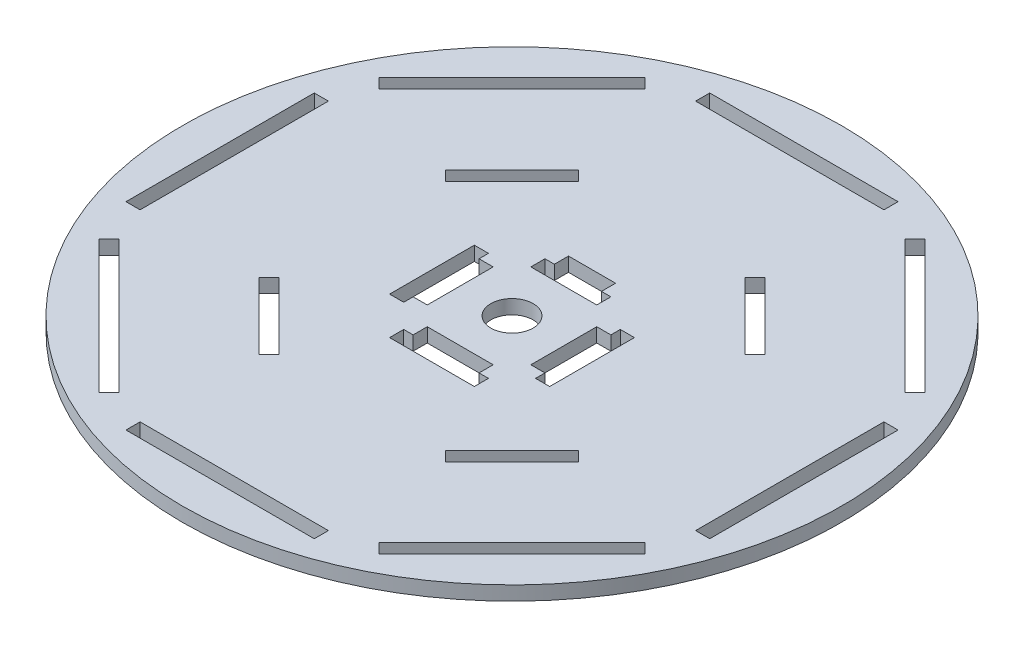
SolidWorks part; units mm, degrees
ref_plane "Alzado" through (0, 0, 0) normal (0, 0, 1) x (1, 0, 0)
ref_plane "Planta" through (0, 0, 0) normal (0, 1, 0) x (1, 0, 0)
ref_plane "Vista lateral" through (0, 0, 0) normal (1, 0, 0) x (0, 0, -1)
sketch "Croquis1" plane through (0, 0, 0) normal (0, 1, 0) x (1, 0, 0)
  line L0 (0, 11) -> (7, 11)
  line L1 (7, 11) -> (7, 14)
  line L2 (24.7487, 24.7487) -> (31.8198, 17.6777)
  line L3 (-7, 14) -> (-7, 11)
  line L4 (-7, 11) -> (0, 11)
  line L5 (11, 0) -> (11, 7)
  line L6 (11, 7) -> (14, 7)
  line L8 (14, -7) -> (11, -7)
  line L9 (11, -7) -> (11, 0)
  line L10 (0, 0) -> (-24.7487, 24.7487) construction
  line L11 (-24.7487, 24.7487) -> (-17.6777, 31.8198)
  line L12 (-17.6777, 31.8198) -> (-19.799, 33.9411)
  line L13 (-14, -7) -> (-11, -7)
  line L14 (-11, -7) -> (-11, 0)
  line L15 (-11, 0) -> (-11, 7)
  line L16 (-11, 7) -> (-14, 7)
  line L17 (-7, -14) -> (-9, -14)
  line L18 (7, -11) -> (7, -14)
  line L19 (0, -11) -> (7, -11)
  line L20 (14, 7) -> (14, 9)
  line L21 (-7, -14) -> (-7, -11)
  line L22 (-7, -11) -> (0, -11)
  line L23 (-19.799, 33.9411) -> (-33.9411, 19.799)
  line L24 (-24.7487, 24.7487) -> (-31.8198, 17.6777)
  line L25 (-31.8198, 17.6777) -> (-33.9411, 19.799)
  line L26 (-7, 14) -> (-5, 14)
  line L27 (5, 14) -> (7, 14)
  line L28 (0, 17) -> (-5, 17)
  line L29 (-5, 17) -> (-5, 14)
  line L30 (0, 17) -> (5, 17)
  line L31 (31.8198, 17.6777) -> (33.9411, 19.799)
  line L32 (33.9411, 19.799) -> (19.799, 33.9411)
  line L33 (17.6777, 31.8198) -> (19.799, 33.9411)
  line L34 (24.7487, 24.7487) -> (17.6777, 31.8198)
  line L35 (24.7487, -24.7487) -> (17.6777, -31.8198)
  line L36 (17.6777, -31.8198) -> (19.799, -33.9411)
  line L37 (19.799, -33.9411) -> (33.9411, -19.799)
  line L38 (31.8198, -17.6777) -> (33.9411, -19.799)
  line L39 (24.7487, -24.7487) -> (31.8198, -17.6777)
  line L40 (-24.7487, -24.7487) -> (-31.8198, -17.6777)
  line L41 (0, 0) -> (0, 62) construction
  line L42 (0, 62) -> (20, 62)
  line L43 (20, 62) -> (20, 59)
  line L44 (20, 59) -> (-20, 59)
  line L45 (-20, 59) -> (-20, 62)
  line L46 (-20, 62) -> (0, 62)
  line L47 (55.8614, 27.5772) -> (27.5772, 55.8614)
  line L48 (27.5772, 55.8614) -> (29.6985, 57.9828)
  line L49 (29.6985, 57.9828) -> (43.8406, 43.8406)
  line L50 (43.8406, 43.8406) -> (57.9828, 29.6985)
  line L51 (57.9828, 29.6985) -> (55.8614, 27.5772)
  line L52 (59, -20) -> (59, 20)
  line L53 (59, 20) -> (62, 20)
  line L54 (62, 20) -> (62, 0)
  line L55 (62, 0) -> (62, -20)
  line L56 (62, -20) -> (59, -20)
  line L57 (27.5772, -55.8614) -> (55.8614, -27.5772)
  line L58 (55.8614, -27.5772) -> (57.9828, -29.6985)
  line L59 (57.9828, -29.6985) -> (43.8406, -43.8406)
  line L60 (43.8406, -43.8406) -> (29.6985, -57.9828)
  line L61 (29.6985, -57.9828) -> (27.5772, -55.8614)
  line L62 (-20, -59) -> (20, -59)
  line L63 (20, -59) -> (20, -62)
  line L64 (20, -62) -> (0, -62)
  line L65 (0, -62) -> (-20, -62)
  line L66 (-20, -62) -> (-20, -59)
  line L67 (-55.8614, -27.5772) -> (-27.5772, -55.8614)
  line L68 (-27.5772, -55.8614) -> (-29.6985, -57.9828)
  line L69 (-29.6985, -57.9828) -> (-43.8406, -43.8406)
  line L70 (-43.8406, -43.8406) -> (-57.9828, -29.6985)
  line L71 (-57.9828, -29.6985) -> (-55.8614, -27.5772)
  line L72 (-59, 20) -> (-59, -20)
  line L73 (-59, -20) -> (-62, -20)
  line L74 (-62, -20) -> (-62, 0)
  line L75 (-62, 0) -> (-62, 20)
  line L76 (-62, 20) -> (-59, 20)
  line L77 (-27.5772, 55.8614) -> (-55.8614, 27.5772)
  line L78 (-55.8614, 27.5772) -> (-57.9828, 29.6985)
  line L79 (-57.9828, 29.6985) -> (-43.8406, 43.8406)
  line L80 (-43.8406, 43.8406) -> (-29.6985, 57.9828)
  line L81 (-29.6985, 57.9828) -> (-27.5772, 55.8614)
  line L82 (-31.8198, -17.6777) -> (-33.9411, -19.799)
  line L83 (-33.9411, -19.799) -> (-19.799, -33.9411)
  line L84 (-17.6777, -31.8198) -> (-19.799, -33.9411)
  line L85 (-24.7487, -24.7487) -> (-17.6777, -31.8198)
  line L86 (5, 17) -> (5, 14)
  line L88 (17, 0) -> (17, -9)
  line L89 (17, -9) -> (14, -9)
  line L90 (14, -9) -> (14, -7)
  line L91 (14, 9) -> (17, 9)
  line L92 (17, 9) -> (17, 0)
  line L94 (0, -17) -> (9, -17)
  line L95 (9, -17) -> (9, -14)
  line L96 (9, -14) -> (7, -14)
  line L97 (-9, -14) -> (-9, -17)
  line L98 (-9, -17) -> (0, -17)
  line L100 (-17, 0) -> (-17, -9)
  line L101 (-17, -9) -> (-14, -9)
  line L102 (-14, -9) -> (-14, -7)
  line L103 (-14, 9) -> (-17, 9)
  line L104 (-17, 9) -> (-17, 0)
  line L105 (-14, 7) -> (-14, 9)
  circle A0 centre (0, 0) radius 4.5
  circle A2 centre (0, 0) radius 70
  point P47 (0, 0)
  point P88 (0, 0)
  point P93 (0, 0)
  dimension "D1" = 9
  dimension "D2" = 14
  dimension "D3" = 140
  dimension "D4" = 7
  dimension "D5" = 3
  dimension "D6" = 14
  dimension "D7" = 35
  dimension "D8" = 3
  dimension "D9" = 10
  dimension "D10" = 3
  dimension "D11" = 20
  dimension "D12" = 10
  dimension "D14" = 62
  dimension "D15" = 20
  dimension "D16" = 3
  dimension "D17" = 40
  dimension "D19" = 3
  dimension "D13" = 4
  dimension "D20" = 5
  dimension "D21" = 3
  dimension "D22" = 5
  dimension "D24" = 9
  dimension "D25" = 18
  dimension "D27" = 9
  dimension "D28" = 18
  dimension "D18" = 8
extrude "Saliente-Extruir1" add sketch "Croquis1" along normal blind 3
